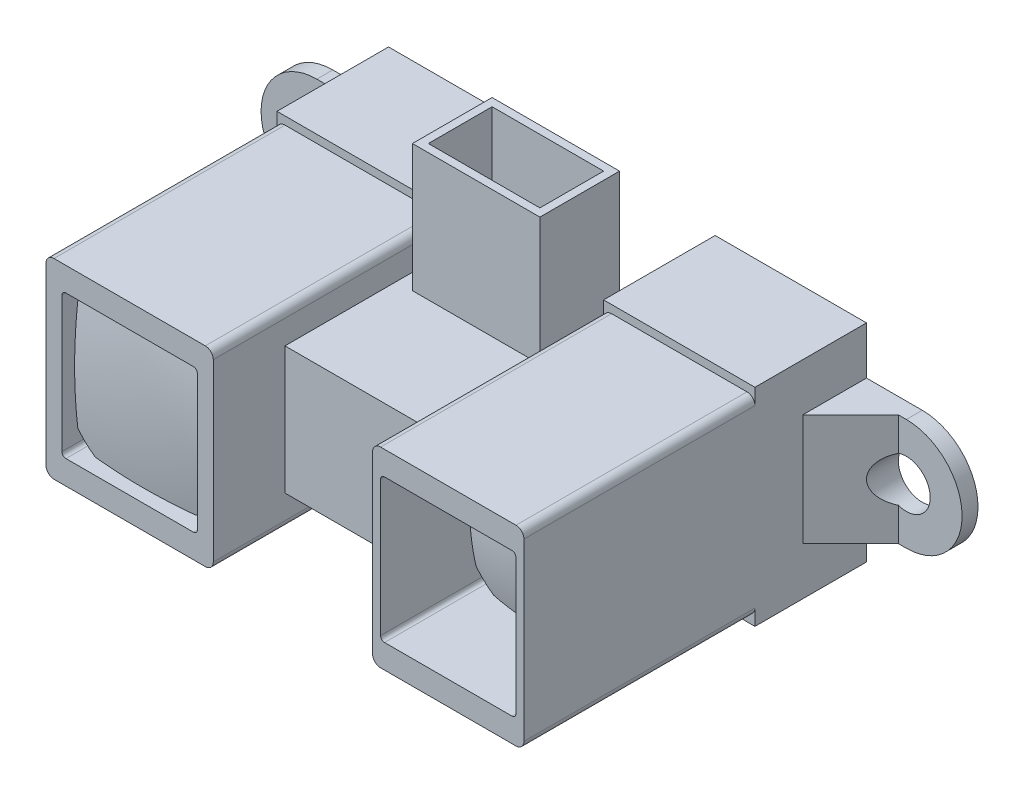
SolidWorks part; units mm, degrees
material "CA"
ref_plane "Front Plane" through (0, 0, 0) normal (0, 0, 1) x (1, 0, 0)
ref_plane "Top Plane" through (0, 0, 0) normal (0, 1, 0) x (1, 0, 0)
ref_plane "Right Plane" through (0, 0, 0) normal (1, 0, 0) x (0, 0, -1)
sketch "Sketch5" plane through (0, 0, 0) normal (0, 0, 1) x (1, 0, 0)
  line L1 (-15, -6.5) -> (15, -6.5)
  line L2 (-15, -6.5) -> (-15, 6.5)
  line L3 (-15, 6.5) -> (15, 6.5)
  line L4 (15, -6.5) -> (15, 6.5)
  line L5 (-15, -6.5) -> (15, 6.5) construction
  line L6 (-15, 6.5) -> (15, -6.5) construction
  point P0 (0, 0)
  dimension "D1" = 30
  dimension "D2" = 13
extrude "Boss-Extrude1" add sketch "Sketch5" along normal blind 7
sketch "Sketch6" plane through (0, 0, 7) normal (0, 0, 1) x (1, 0, 0)
  line L0 (-9.75, 0) -> (10.25, 0) construction
  line L1 (-4.5, -6) -> (-15, -6)
  line L2 (-4.5, -6) -> (-4.5, 6)
  line L3 (-4.5, 6) -> (-15, 6)
  line L4 (-15, -6) -> (-15, 6)
  line L5 (-4.5, -6) -> (-15, 6) construction
  line L6 (-4.5, 6) -> (-15, -6) construction
  line L7 (15, -6) -> (5.5, -6)
  line L8 (15, -6) -> (15, 6)
  line L9 (15, 6) -> (5.5, 6)
  line L10 (5.5, -6) -> (5.5, 6)
  line L11 (15, -6) -> (5.5, 6) construction
  line L12 (15, 6) -> (5.5, -6) construction
  line L13 (-15, 6.5) -> (-15, -6.5) construction
  line L14 (15, -6.5) -> (15, 6.5) construction
  line L16 (14.5, -4.5) -> (6, -4.5)
  line L17 (14.5, -4.5) -> (14.5, 4.5)
  line L18 (14.5, 4.5) -> (6, 4.5)
  line L19 (6, -4.5) -> (6, 4.5)
  line L20 (14.5, -4.5) -> (6, 4.5) construction
  line L21 (14.5, 4.5) -> (6, -4.5) construction
  line L22 (-5.5, -4.5) -> (-14, -4.5)
  line L23 (-5.5, -4.5) -> (-5.5, 4.5)
  line L24 (-5.5, 4.5) -> (-14, 4.5)
  line L25 (-14, -4.5) -> (-14, 4.5)
  line L26 (-5.5, -4.5) -> (-14, 4.5) construction
  line L27 (-5.5, 4.5) -> (-14, -4.5) construction
  point P0 (-9.75, 0)
  point P5 (10.25, 0)
  dimension "D1" = 12
  dimension "D2" = 9.5
  dimension "D3" = 1.5
  dimension "D4" = 0.5
  dimension "D5" = 10.5
  dimension "D6" = 1
extrude "Boss-Extrude2" add sketch "Sketch6" along normal blind 14.5
sketch "Sketch7" plane through (0, 0, 7) normal (0, 0, 1) x (1, 0, 0)
  line L0 (-4.5, -6) -> (-4.5, 6) construction
  line L1 (-4.5, 4) -> (5.5, 4)
  line L2 (-4.5, 4) -> (-4.5, -4)
  line L3 (-4.5, -4) -> (5.5, -4)
  line L4 (5.5, 4) -> (5.5, -4)
  line L5 (5.5, 6) -> (5.5, -6) construction
  line L6 (0, 4) -> (0, -4) construction
  dimension "D1" = 8
extrude "Boss-Extrude3" add sketch "Sketch7" along normal blind 10
fillet "Fillet1" radius 0.25 8 edges at (6, 4.5, 14.25) (6, -4.5, 14.25) (14.5, -4.5, 14.25) (-5.5, -4.5, 14.25) (14.5, 4.5, 14.25) (-5.5, 4.5, 14.25) (-14, 4.5, 14.25) (-14, -4.5, 14.25)
fillet "Fillet2" radius 0.5 8 edges at (15, -6, 14.25) (5.5, -6, 14.25) (-4.5, -6, 14.25) (5.5, 6, 14.25) (15, 6, 14.25) (-4.5, 6, 14.25)
sketch "Sketch8" plane through (0, 0, 0) normal (0, 0, -1) x (-1, 0, 0)
  line L0 (-18.5, 3.5) -> (-15, 3.5)
  line L1 (-15, -6.5) -> (-15, 6.5) construction
  line L2 (-15, 3.5) -> (-15, -3.5)
  line L3 (-15, -3.5) -> (-18.5, -3.5)
  line L4 (0, 0) -> (0, 6.5) construction
  line L5 (-15, 6.5) -> (15, 6.5) construction
  line L6 (15, -3.5) -> (18.5, -3.5)
  line L7 (15, 3.5) -> (15, -3.5)
  line L8 (18.5, 3.5) -> (15, 3.5)
  arc A0 (-18.5, 3.5) -> (-18.5, -3.5) centre (-18.5, 0) ccw
  circle A1 centre (-18.5, 0) radius 1.5
  circle A2 centre (18.5, 0) radius 1.5
  arc A3 (18.5, 3.5) -> (18.5, -3.5) centre (18.5, 0) cw
  dimension "D2" = 3
  dimension "D1" = 7
extrude "Boss-Extrude4" add sketch "Sketch8" against normal blind 1
chamfer "Chamfer1" distance 3 angle 45 2 edges at (-15, 0, 1) (15, 0, 1)
sketch "Sketch10" plane through (0, 0, 17) normal (0, 0, 1) x (1, 0, 0)
  line L0 (-18, 3.5) -> (-15, 3.5) construction
  line L3 (-15, 3.5) -> (-15, -3.5) construction
  line L4 (-15, -3.5) -> (-18, -3.5) construction
  line L6 (-18.5, 3.5) -> (-15, 3.5)
  line L7 (-15, 3.5) -> (-15, -3.5)
  line L8 (-15, -3.5) -> (-18.5, -3.5)
  line L9 (-17, 3.5) -> (-17, 3.1623)
  line L10 (-17, -3.1623) -> (-17, -3.5)
  line L11 (0, 0) -> (0, 8.3408) construction
  line L12 (17, -3.1623) -> (17, -3.5)
  line L13 (17, 3.5) -> (17, 3.1623)
  line L14 (15, -3.5) -> (18.5, -3.5)
  line L15 (15, 3.5) -> (15, -3.5)
  line L16 (18.5, 3.5) -> (15, 3.5)
  arc A0 (-18.5, 3.5) -> (-18.5, -3.5) centre (-18.5, 0) ccw
  arc A1 (-18, -1.4142) -> (-18, 1.4142) centre (-18.5, 0) ccw construction
  arc A2 (-17, -3.1623) -> (-17, 3.1623) centre (-18.5, 0) ccw
  arc A4 (17, -3.1623) -> (17, 3.1623) centre (18.5, 0) cw
  arc A6 (18.5, 3.5) -> (18.5, -3.5) centre (18.5, 0) cw
extrude "Cut-Extrude1" cut sketch "Sketch10" against normal up to vertex (16 mm away) contours A2 L9 L6 A0 L8 L10 region at (-18.4904, 0, 17) up to point (-18, -3.5, 1)
ref_plane "Plane1" through (0, 0, 0) normal (0, 1, 0) x (-1, 0, 0)
sketch "Sketch11" plane through (0, 0, 0) normal (0, 1, 0) x (-1, 0, 0)
  line L0 (9.75, 21.5) -> (9.75, 7) construction
  line L1 (5, 21.5) -> (14.5, 21.5) construction
  line L2 (5, 7) -> (14.5, 7) construction
  line L4 (9.75, 21) -> (8.6553, 21) construction
  line L5 (15.25, 20.5) -> (15.25, 19)
  line L6 (15.25, 19) -> (9.75, 19)
  line L7 (9.75, 19) -> (9.75, 21)
  arc A0 (9.75, 21) -> (15.25, 20.5) centre (9.75, -9.5) cw
  dimension "D1" = 0.5
  dimension "D2" = 0.5
  dimension "D3" = 2
  dimension "D4" = 5.5
revolve "Revolve1" add sketch "Sketch11" angle 360 about L7
sketch "Sketch12" plane through (0, 0, 21.5) normal (0, 0, 1) x (1, 0, 0)
  line L0 (-14, 4.25) -> (-14, -4.25) construction
  line L1 (-14, 4.25) -> (-14, -4.25)
  line L2 (-13.75, -4.5) -> (-5.75, -4.5) construction
  line L3 (-5.75, 4.5) -> (-13.75, 4.5) construction
  line L4 (-5.5, -4.25) -> (-5.5, 4.25) construction
  line L5 (-13.75, -4.5) -> (-5.75, -4.5)
  line L6 (-5.75, 4.5) -> (-13.75, 4.5)
  line L7 (-5.5, -4.25) -> (-5.5, 4.25)
  arc A0 (-14, -4.25) -> (-13.75, -4.5) centre (-13.75, -4.25) ccw construction
  arc A1 (-13.75, 4.5) -> (-14, 4.25) centre (-13.75, 4.25) ccw construction
  arc A2 (-5.5, 4.25) -> (-5.75, 4.5) centre (-5.75, 4.25) ccw construction
  arc A3 (-5.75, -4.5) -> (-5.5, -4.25) centre (-5.75, -4.25) ccw construction
  arc A4 (-14, -4.25) -> (-13.75, -4.5) centre (-13.75, -4.25) ccw
  arc A5 (-13.75, 4.5) -> (-14, 4.25) centre (-13.75, 4.25) ccw
  arc A6 (-5.5, 4.25) -> (-5.75, 4.5) centre (-5.75, 4.25) ccw
  arc A7 (-5.75, -4.5) -> (-5.5, -4.25) centre (-5.75, -4.25) ccw
extrude "Cut-Extrude2" cut sketch "Sketch12" against normal up to vertex (4.5 mm away) flip side to cut up to point (-4.5, 4, 17)
ref_plane "Plane2" through (0, 0, 0) normal (0, 1, 0) x (-1, 0, 0)
sketch "Sketch13" plane through (0, 0, 0) normal (0, 1, 0) x (-1, 0, 0)
  line L0 (-10.25, 21.5) -> (-10.25, 7) construction
  line L1 (-14.5, 21.5) -> (-6, 21.5) construction
  line L2 (-14.5, 7) -> (-6, 7) construction
  line L3 (-10.25, 14.5) -> (-15.75, 14.5)
  line L4 (-15.75, 14.5) -> (-15.75, 15.5)
  line L5 (-10.25, 16.5) -> (-10.25, 14.5)
  line L6 (-10.25, 16.5) -> (-6.763, 16.5) construction
  arc A0 (-15.75, 15.5) -> (-10.25, 16.5) centre (-10.25, 0.875) cw
  dimension "D1" = 5
  dimension "D2" = 2
  dimension "D3" = 1
  dimension "D4" = 5.5
revolve "Revolve2" add sketch "Sketch13" angle 360 about L5
sketch "Sketch14" plane through (0, 0, 21.5) normal (0, 0, 1) x (1, 0, 0)
  line L0 (14.25, 4.5) -> (6.25, 4.5) construction
  line L1 (14.5, -4.25) -> (14.5, 4.25) construction
  line L2 (6, 4.25) -> (6, -4.25) construction
  line L3 (6.25, -4.5) -> (14.25, -4.5) construction
  line L4 (14.25, 4.5) -> (6.25, 4.5)
  line L5 (14.5, -4.25) -> (14.5, 4.25)
  line L6 (6, 4.25) -> (6, -4.25)
  line L7 (6.25, -4.5) -> (14.25, -4.5)
  arc A0 (14.5, 4.25) -> (14.25, 4.5) centre (14.25, 4.25) ccw construction
  arc A1 (6, -4.25) -> (6.25, -4.5) centre (6.25, -4.25) ccw construction
  arc A2 (14.25, -4.5) -> (14.5, -4.25) centre (14.25, -4.25) ccw construction
  arc A3 (6.25, 4.5) -> (6, 4.25) centre (6.25, 4.25) ccw construction
  arc A4 (14.5, 4.25) -> (14.25, 4.5) centre (14.25, 4.25) ccw
  arc A5 (6, -4.25) -> (6.25, -4.5) centre (6.25, -4.25) ccw
  arc A6 (14.25, -4.5) -> (14.5, -4.25) centre (14.25, -4.25) ccw
  arc A7 (6.25, 4.5) -> (6, 4.25) centre (6.25, 4.25) ccw
extrude "Cut-Extrude5" cut sketch "Sketch14" against normal up to vertex (14.5 mm away) flip side to cut up to point (-4.5, 4, 7)
sketch "Sketch15" plane through (0, 0, 0) normal (0, 0, -1) x (-1, 0, 0)
  line L0 (-15, 6.5) -> (15, 6.5) construction
  line L1 (14, -5.5) -> (-14, -5.5)
  line L2 (14, -5.5) -> (14, 5.5)
  line L3 (14, 5.5) -> (4.5, 5.5)
  line L4 (-14, -5.5) -> (-14, 5.5)
  line L5 (14, -5.5) -> (-14, 5.5) construction
  line L6 (14, 5.5) -> (-14, -5.5) construction
  line L7 (-15, 3.5) -> (-15, 6.5) construction
  line L8 (-5.5, 5.5) -> (-5.5, 6.5)
  line L9 (-5.5, 6.5) -> (4.5, 6.5)
  line L10 (4.5, 6.5) -> (4.5, 5.5)
  line L11 (-5.5, 5.5) -> (-14, 5.5)
  line L12 (4.5, -5.5) -> (4.5, 5.5) construction
  line L13 (-5.5, 5.5) -> (-5.5, 4) construction
  point P0 (0, 0)
  dimension "D1" = 1
  dimension "D2" = 1
extrude "Cut-Extrude6" cut sketch "Sketch15" against normal offset from surface (6 mm away) 1 up to face at (-0.1458, -5.5762, 7)
sketch "Sketch16" plane through (0, 0, 6) normal (0, 0, -1) x (-1, 0, 0)
  line L3 (-5.5, 6.5) -> (4.5, 6.5)
  line L4 (-5.5, 6.5) -> (-5.5, 4)
  line L5 (-5.5, 4) -> (4.5, 4)
  line L8 (4.5, 6.5) -> (4.5, 4)
extrude "Cut-Extrude7" cut sketch "Sketch16" against normal up to vertex (1 mm away) up to point (5.5, 4, 7)
sketch "Sketch17" plane through (0, 4, 0) normal (0, 1, 0) x (1, 0, 0)
  line L0 (0.5, -17) -> (0.5, -7.5) construction
  line L1 (4.5, -10) -> (-3.5, -10)
  line L2 (4.5, -10) -> (4.5, -5)
  line L3 (4.5, -5) -> (-3.5, -5)
  line L4 (-3.5, -10) -> (-3.5, -5)
  line L5 (4.5, -10) -> (-3.5, -5) construction
  line L6 (4.5, -5) -> (-3.5, -10) construction
  line L8 (5.5, -17) -> (-4.5, -17) construction
  line L9 (-4.5, 0) -> (-15, 0) construction
  point P0 (0.5, -7.5)
  dimension "D1" = 8
  dimension "D2" = 5
  dimension "D3" = 5
extrude "Boss-Extrude5" add sketch "Sketch17" along normal blind 8 separate body
shell "Shell1" thickness 0.5 removed face at (0.5, 12, 7.5)
